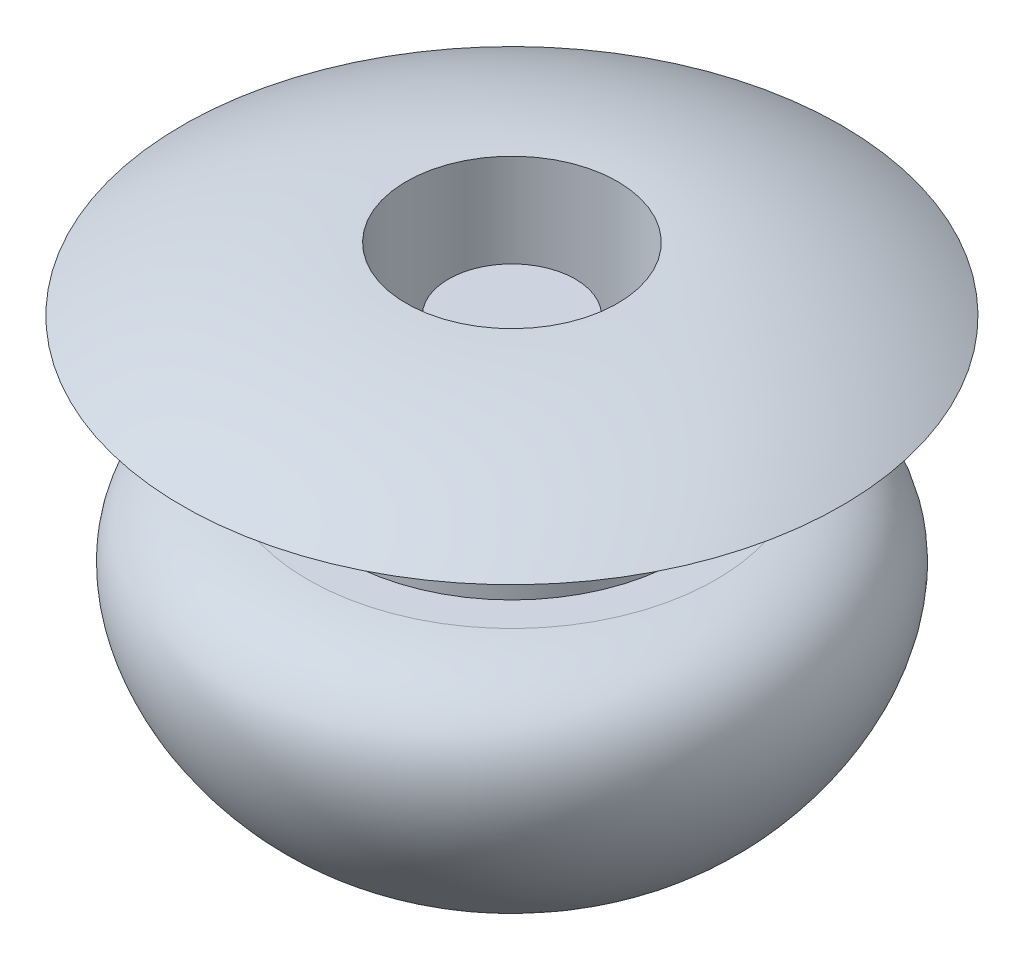
SolidWorks part; units mm, degrees
material "AISI 316 Stal nierdzewna odprężona (SS)"
ref_plane "Płaszczyzna przednia" through (0, 0, 0) normal (0, 0, 1) x (1, 0, 0)
ref_plane "Płaszczyzna górna" through (0, 0, 0) normal (0, 1, 0) x (1, 0, 0)
ref_plane "Płaszczyzna prawa" through (0, 0, 0) normal (1, 0, 0) x (0, 0, -1)
sketch "Szkic1" plane through (0, 0, 0) normal (1, 0, 0) x (0, 0, -1)
  line L1 (0, 0) -> (-0.75, 0)
  line L2 (-0.75, 0) -> (-0.75, -1.7007)
  line L3 (-0.75, -1.7007) -> (-1.25, -1.7007)
  line L4 (-1.25, -1.7007) -> (-1.25, 0.75)
  line L5 (-3.9, 0) -> (-2, 0)
  line L6 (-2, 0) -> (-2, -1.5)
  line L7 (-2, -1.5) -> (-2.4139, -1.5)
  line L8 (0, 0) -> (0, 0.4842) construction
  line L9 (0, -1.7007) -> (0, 0)
  line L10 (0, -1.7007) -> (0, -3.2007)
  line L11 (65.5531, -1.5) -> (69.5531, -1.5) construction
  arc A0 (-1.25, 0.75) -> (-3.9, 0) centre (-1.25, -4.3067) ccw
  ellipse E0 centre (0, -2.4507) end of major axis (-1.75, -2.4507) minor radius 0.75 (-0.956, -3.0789) -> (0, -3.2007) ccw
  spline S0 degree 3 poles (-2.4139, -1.5) (-3.8675, -1.6696) (-3.5289, -3.802) (-1.084, -5.3735) (-0.2718, -3.3749) (-0.956, -3.0789) knots 0 0 0 0 0.464993 0.721928 1 1 1 1
  dimension "D1" = 7.8
  dimension "D2" = 2.5
  dimension "D3" = 4
  dimension "D4" = 0.75
  dimension "D5" = 1.5
  dimension "D6" = 1.5
  dimension "D7" = 3.5
  dimension "D8" = 3.1855
  dimension "D9" = 2.5026
  dimension "D10" = 1.9
  dimension "D11" = 1.5789
  dimension "D12" = 0.5792
  dimension "D13" = 4.8278
  dimension "D14" = 3.3858
  dimension "D15" = 2.8395
  dimension "D16" = 1.25
  dimension "D17" = 0.6409
  dimension "D18" = 0.956
revolve "Obrót1" add sketch "Szkic1" angle 360 about L8
